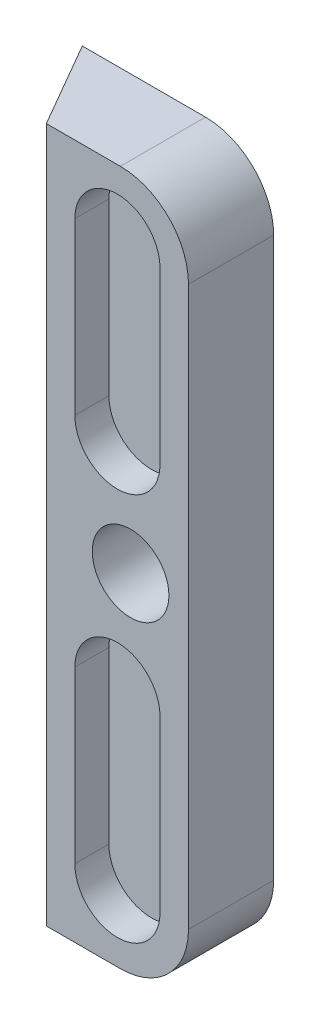
SolidWorks part; units mm, degrees
material "Сплав 2024"
ref_plane "Спереди" through (0, 0, 0) normal (0, 0, 1) x (1, 0, 0)
ref_plane "Сверху" through (0, 0, 0) normal (0, 1, 0) x (1, 0, 0)
ref_plane "Справа" through (0, 0, 0) normal (1, 0, 0) x (0, 0, -1)
sketch "Эскиз1" plane through (0, 0, 0) normal (0, 1, 0) x (1, 0, 0)
  line L0 (0, 0) -> (0, 5)
  line L1 (0, 5) -> (-11.2321, 5)
  line L2 (0, 0) -> (-8.3453, 0)
  line L3 (-8.3453, 0) -> (-11.2321, 5)
  line L4 (-9.5, 2) -> (-9.5, 0) construction
  line L5 (-8.3453, 0) -> (-9.4483, 0) construction
  dimension "D1" = 2
  dimension "D2" = 60
  dimension "D3" = 5
  dimension "D4" = 9.5
extrude "Бобышка-Вытянуть1" add sketch "Эскиз1" along normal blind 40.8
fillet "Скругление1" radius 4 2 edges at (0, 0, -2.5) (0, 40.8, -2.5)
sketch "Эскиз4" plane through (0, 0, 0) normal (0, 0, 1) x (1, 0, 0)
  line L0 (0, 20.4) -> (-8.3453, 20.4) construction
  line L1 (0, 36.8) -> (0, 4) construction
  line L2 (-8.3453, 40.8) -> (-8.3453, 0) construction
  line L3 (-4.1726, 20.4) -> (-4.1726, 33.5057) construction
  line L4 (-4.1726, 36.8) -> (-4.1726, 26.8) construction
  line L5 (-1.6726, 36.8) -> (-1.6726, 26.8)
  line L6 (-6.6726, 36.8) -> (-6.6726, 26.8)
  line L7 (-8.3453, 40.8) -> (-4, 40.8) construction
  line L8 (-4.1726, 4) -> (-4.1726, 14) construction
  line L9 (-1.6726, 4) -> (-1.6726, 14)
  line L10 (-6.6726, 4) -> (-6.6726, 14)
  arc A0 (-1.6726, 36.8) -> (-6.6726, 36.8) centre (-4.1726, 36.8) ccw
  arc A1 (-6.6726, 26.8) -> (-1.6726, 26.8) centre (-4.1726, 26.8) ccw
  arc A2 (-1.6726, 4) -> (-6.6726, 4) centre (-4.1726, 4) cw
  arc A3 (-6.6726, 14) -> (-1.6726, 14) centre (-4.1726, 14) cw
  point P10 (-4.1726, 31.8)
  point P19 (-4.1726, 9)
  dimension "D1" = 10
  dimension "D2" = 5
  dimension "D3" = 4
extrude "Вырез-Вытянуть1" cut sketch "Эскиз4" against normal offset from surface (2 mm away) 3 up to face at (-4.8012, 20.4, -5)
sketch "Эскиз5" plane through (0, 0, 0) normal (0, 0, 1) x (1, 0, 0)
  line L0 (0, 20.4) -> (-5.6917, 20.4) construction
  line L1 (0, 36.8) -> (0, 4) construction
  point P4 (-3.4, 20.4)
  dimension "D1" = 3.4
hole_wizard "Отверстие с зазором M41" positions "Эскиз7" profile "Эскиз6" hole size "M4" standard "Ansi Metric" end condition through all
sketch "Эскиз7" plane through (0, 0, 0) normal (0, 0, 1) x (1, 0, 0)
  point P0 (-3.4, 20.4)
sketch "Эскиз6" plane through (-3.4, 20.4, 0) normal (1, 0, 0) x (0, -1, 0)
  line L0 (0, 0) -> (0, 5)
  line L1 (0, 5) -> (2.25, 5)
  line L2 (2.25, 5) -> (2.25, 0)
  line L5 (2.25, 0) -> (0, 0)
  line L11 (0, -6.35) -> (0, 107.95) construction
  dimension "Диаметр сквозного отверстия" = 4.5
  dimension "Глубина сквозного отверстия" = 5
